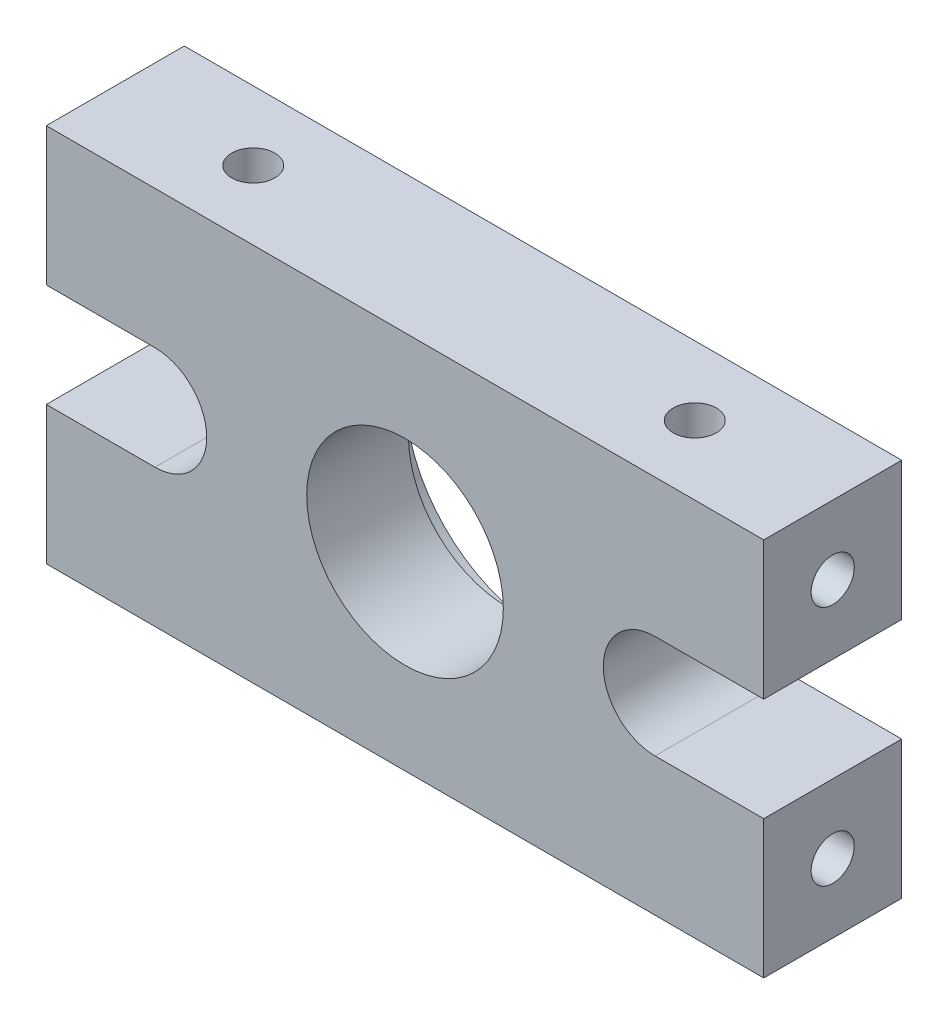
SolidWorks part; units mm, degrees
ref_plane "Front Plane" through (0, 0, 0) normal (0, 0, 1) x (1, 0, 0)
ref_plane "Top Plane" through (0, 0, 0) normal (0, 1, 0) x (1, 0, 0)
ref_plane "Right Plane" through (0, 0, 0) normal (1, 0, 0) x (0, 0, -1)
sketch "Sketch1" plane through (0, 0, 0) normal (0, 0, 1) x (1, 0, 0)
  line L0 (0, 0) -> (41.6, 0)
  line L1 (41.6, 0) -> (41.6, 8)
  line L2 (41.6, 22) -> (0, 22)
  line L3 (0, 8) -> (0, 0)
  line L4 (0, 8) -> (6.3, 8)
  line L5 (6.3, 14) -> (0, 14)
  line L6 (0, 14) -> (0, 22)
  line L7 (41.6, 8) -> (35.3, 8)
  line L8 (35.3, 14) -> (41.6, 14)
  line L9 (41.6, 14) -> (41.6, 22)
  circle A0 centre (20.8, 11) radius 5.7
  arc A1 (6.3, 8) -> (6.3, 14) centre (6.3, 11) ccw
  arc A2 (35.3, 8) -> (35.3, 14) centre (35.3, 11) cw
  dimension "D1" = 11.4
  dimension "D6" = 3
  dimension "D2" = 41.6
  dimension "D3" = 22
  dimension "D4" = 11
  dimension "D5" = 20.8
  dimension "D7" = 6.3
extrude "Boss-Extrude1" add sketch "Sketch1" along normal blind 8
hole_wizard "Tap Drill for M3x0.5 Tap1" positions "Sketch3" profile "Sketch2" hole size "M3x0.5" standard "ANSI Metric"
sketch "Sketch3" plane through (41.6, 0, 0) normal (1, 0, 0) x (0, 0, -1)
  line L0 (-8, 0) -> (-8, 8) construction
  line L1 (-8, 0) -> (0, 0) construction
  line L2 (-8, 22) -> (0, 22) construction
  point P0 (-4, 18)
  point P2 (-4, 4)
  dimension "D1" = 4
  dimension "D2" = 4
  dimension "D3" = 4
sketch "Sketch2" plane through (41.6, 18, 4) normal (0, 1, 0) x (0, 0, -1)
  line L0 (0, 0) -> (0, 5.7511)
  line L1 (0, 5.7511) -> (1.25, 5)
  line L2 (1.25, 5) -> (1.25, 0)
  line L5 (1.25, 0) -> (0, 0)
  line L10 (0, 5.7511) -> (-1.25, 5) construction
  line L11 (0, -6.35) -> (0, 107.95) construction
  dimension "Hole Dia." = 2.5
  dimension "Hole Depth" = 5
  dimension "Drill Angle" = 118
hole_wizard "Tap Drill for M3x0.5 Tap2" positions "Sketch5" profile "Sketch4" hole size "M3x0.5" standard "ANSI Metric"
sketch "Sketch5" plane through (0, 0, 0) normal (-1, 0, 0) x (0, 0, 1)
  line L0 (8, 22) -> (8, 14) construction
  line L1 (8, 22) -> (0, 22) construction
  line L2 (8, 0) -> (0, 0) construction
  point P0 (4, 4)
  point P2 (4, 18)
  dimension "D1" = 4
  dimension "D2" = 4
  dimension "D3" = 4
sketch "Sketch4" plane through (0, 4, 4) normal (0, 1, 0) x (0, 0, 1)
  line L0 (0, 0) -> (0, 5.7511)
  line L1 (0, 5.7511) -> (1.25, 5)
  line L2 (1.25, 5) -> (1.25, 0)
  line L5 (1.25, 0) -> (0, 0)
  line L10 (0, 5.7511) -> (-1.25, 5) construction
  line L11 (0, -6.35) -> (0, 107.95) construction
  dimension "Hole Dia." = 2.5
  dimension "Hole Depth" = 5
  dimension "Drill Angle" = 118
hole_wizard "Tap Drill for M3x0.5 Tap3" positions "Sketch7" profile "Sketch6" hole size "M3x0.5" standard "ANSI Metric"
sketch "Sketch7" plane through (0, 22, 0) normal (0, 1, 0) x (1, 0, 0)
  line L0 (0, -8) -> (0, 0) construction
  line L1 (41.6, 0) -> (0, 0) construction
  line L2 (41.6, -8) -> (41.6, 0) construction
  point P0 (33.6, -4)
  point P2 (8, -4)
  dimension "D1" = 8
  dimension "D2" = 4
  dimension "D3" = 8
sketch "Sketch6" plane through (33.6, 22, 4) normal (1, 0, 0) x (0, 0, 1)
  line L0 (0, 0) -> (0, 5.7511)
  line L1 (0, 5.7511) -> (1.25, 5)
  line L2 (1.25, 5) -> (1.25, 0)
  line L5 (1.25, 0) -> (0, 0)
  line L10 (0, 5.7511) -> (-1.25, 5) construction
  line L11 (0, -6.35) -> (0, 107.95) construction
  dimension "Hole Dia." = 2.5
  dimension "Hole Depth" = 5
  dimension "Drill Angle" = 118
sketch "Sketch8" plane through (0, 0, 0) normal (0, 0, -1) x (-1, 0, 0)
  circle A0 centre (-20.8, 11) radius 8
  dimension "D1" = 16
extrude "Cut-Extrude1" cut sketch "Sketch8" against normal blind 2.1
